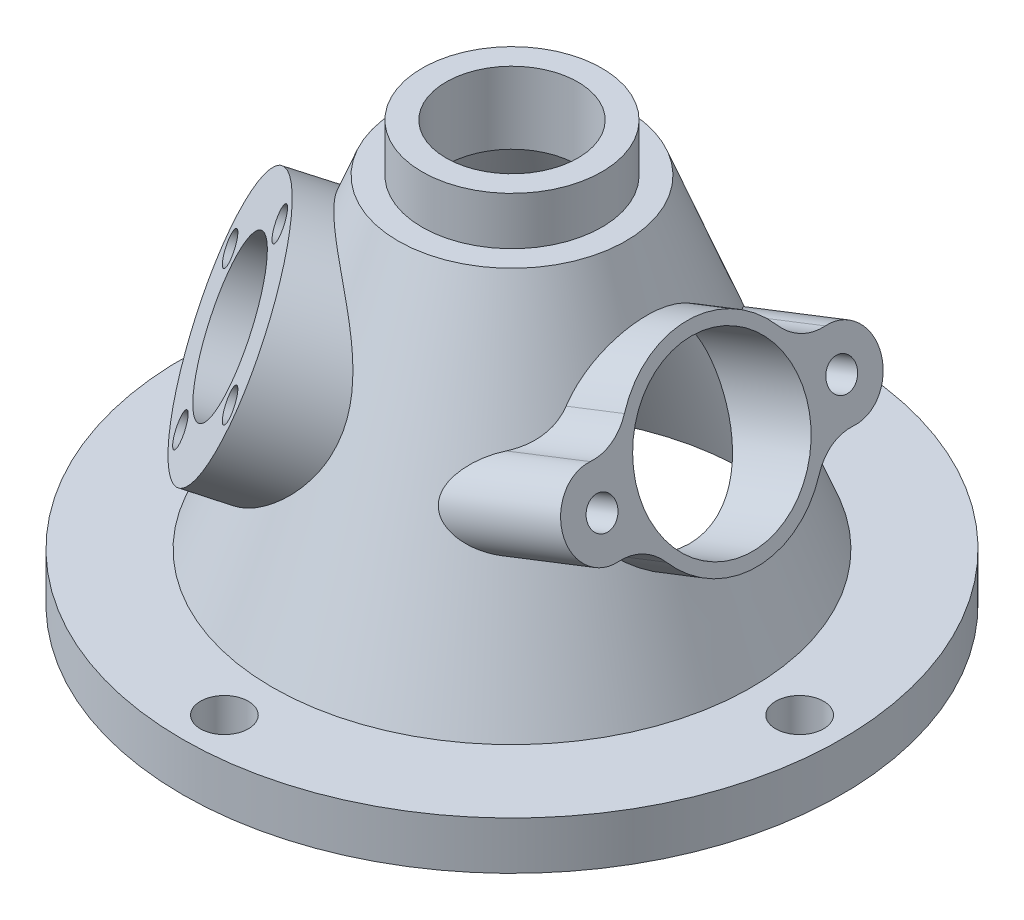
SolidWorks part; units mm, degrees
ref_plane "Front Plane" through (0, 0, 0) normal (0, 0, 1) x (1, 0, 0)
ref_plane "Top Plane" through (0, 0, 0) normal (0, 1, 0) x (1, 0, 0)
ref_plane "Right Plane" through (0, 0, 0) normal (1, 0, 0) x (0, 0, -1)
sketch "Sketch1" plane through (0, 0, 0) normal (0, 0, 1) x (1, 0, 0)
  line L0 (0, 0) -> (-11306.7437, 0) construction
  line L1 (0, 0) -> (0, -50000) construction
  line L3 (27.5, 0) -> (27.5, 4)
  line L4 (27.5, 4) -> (20, 4)
  line L5 (20, 4) -> (9.5, 31)
  line L6 (9.5, 31) -> (7.5, 31)
  line L7 (7.5, 31) -> (7.5, 35)
  line L8 (7.5, 35) -> (5.5, 35)
  line L9 (5.5, 35) -> (5.5, 29)
  line L10 (5.5, 29) -> (8.1319, 29)
  line L11 (8.1319, 29) -> (19.4096, 0)
  line L12 (19.4096, 0) -> (27.5, 0)
  dimension "D1" = 19
  dimension "D2" = 15
  dimension "D3" = 4
  dimension "D4" = 2
  dimension "D5" = 2
  dimension "D6" = 4
  dimension "D7" = 55
  dimension "D8" = 40
  dimension "D9" = 35
  dimension "D10" = 2
revolve "Revolve1" add sketch "Sketch1" angle 360 about L1
sketch "Sketch2" plane through (0, 4, 0) normal (0, 1, 0) x (1, 0, 0)
  line L0 (0, 0) -> (-50000, 0) construction
  line L1 (0, 0) -> (0, -50000) construction
  circle A0 centre (0, 24) radius 2
  circle A1 centre (24, 0) radius 2
  circle A2 centre (0, -24) radius 2
  circle A3 centre (-24, 0) radius 2
  point P7 (-25.7521, -3.72)
  point P16 (0, 0)
  dimension "D1" = 24
  dimension "D2" = 4
  dimension "D3" = 4
extrude "Cut-Extrude1" cut sketch "Sketch2" against normal blind 10
sketch "Sketch4" plane through (0, 35, 0) normal (0, 1, 0) x (1, 0, 0)
  line L0 (0, 7.5) -> (0, -7.5)
  line L1 (-5.3033, 5.3033) -> (5.3033, -5.3033)
  circle A0 centre (0, 0) radius 7.5 construction
  circle A1 centre (0, 0) radius 7.5 construction
  point P10 (0, 0)
  dimension "D1" = 45
ref_plane "Plane1" through (11.8453, 4.6183, 0) normal (0.9317, 0.3633, 0) x (0, 0, 1)
ref_plane "Plane2" through (22.0939, 8.6141, 0) normal (0.9317, 0.3633, 0) x (0, 0, 1)
sketch "Sketch5" plane through (22.0939, 8.6141, 0) normal (0.9317, 0.3633, 0) x (0, 0, 1)
  line L0 (-7.5, -32.6092) -> (7.5, -32.6092) construction
  line L1 (0, -12.6092) -> (0, 0) construction
  line L2 (-10, -12.6092) -> (10, -12.6092) construction
  arc A0 (6.3813, -7.7843) -> (-6.3813, -7.7843) centre (0, -12.6092) ccw
  circle A1 centre (0, -12.6092) radius 7
  circle A2 centre (-10, -12.6092) radius 1.25
  circle A3 centre (10, -12.6092) radius 1.25
  arc A5 (9.8081, -15.8535) -> (9.8081, -9.3649) centre (10, -12.6092) ccw
  arc A6 (-9.8081, -9.3649) -> (-9.8081, -15.8535) centre (-10, -12.6092) ccw
  arc A7 (9.8081, -15.8535) -> (6.3813, -17.4341) centre (9.5719, -19.8465) ccw
  arc A8 (9.8081, -9.3649) -> (6.3813, -7.7843) centre (9.5719, -5.3718) cw
  arc A9 (-9.8081, -9.3649) -> (-6.3813, -7.7843) centre (-9.5719, -5.3718) ccw
  arc A10 (-9.8081, -15.8535) -> (-6.3813, -17.4341) centre (-9.5719, -19.8465) cw
  arc A11 (-6.3813, -17.4341) -> (6.3813, -17.4341) centre (0, -12.6092) ccw
  point P10 (0, -12.6092)
  dimension "D1" = 20
  dimension "D2" = 16
  dimension "D3" = 14
  dimension "D5" = 2.5
  dimension "D6" = 8
  dimension "D7" = 3.25
  dimension "D4" = 20
extrude "Boss-Extrude1" add sketch "Sketch5" against normal up to next
extrude "Cut-Extrude2" cut sketch "Sketch5<3>" against normal blind 20 contours A1 | A2 | A3 region at (17.5136, 20.3619, 0) region at (17.5136, 20.3619, -10)
sketch "Sketch5<3>" plane through (22.0939, 8.6141, 0) normal (0.9317, 0.3633, 0) x (0, 0, 1) same geometry as "Sketch5"
ref_plane "Plane3" through (-8.4393, 4.7013, 8.4393) normal (-0.6579, 0.3665, 0.6579) x (0.7071, 0, 0.7071)
ref_plane "Plane4" through (-15.0183, 8.3663, 15.0183) normal (-0.6579, 0.3665, 0.6579) x (0.7071, 0, 0.7071)
sketch "Sketch7" plane through (-15.0183, 8.3663, 15.0183) normal (-0.6579, 0.3665, 0.6579) x (0.7071, 0, 0.7071)
  line L0 (0, 12.2425) -> (0, -49987.7575) construction
  line L1 (-7.5, 32.5646) -> (7.5, 32.5646) construction
  circle A0 centre (0, 12.5646) radius 10
  circle A1 centre (0, 12.5646) radius 6
  circle A2 centre (0, 12.5646) radius 8 construction
  circle A3 centre (0, 20.5646) radius 1.25
  circle A4 centre (8, 12.5646) radius 1.25
  circle A5 centre (0, 4.5646) radius 1.25
  circle A6 centre (-8, 12.5646) radius 1.25
  point P11 (0, 0)
  point P12 (-7.6386, 10.1874)
  point P13 (0, 0)
  point P20 (0, 12.5646)
  dimension "D1" = 20
  dimension "D2" = 12
  dimension "D3" = 16
  dimension "D5" = 2.5
  dimension "D4" = 20
  dimension "D6" = 4
extrude "Boss-Extrude2" add sketch "Sketch7" against normal up to next contours A4 | A6 | A5 | A0 A6 A5 A4 A3 A1 | A3 | A1 region at (-18.6332, 20.0567, 4.8911) region at (-6.1053, 20.0567, 17.419) region at (-13.8354, 12.6133, 13.8354) region at (-17.419, 20.0567, 6.1053)
extrude "Cut-Extrude3" cut sketch "Sketch7<3>" against normal blind 15 contours A1 | A4 | A3 | A5 | A6 region at (-11.7622, 20.0567, 11.7622) region at (-9.6889, 27.5, 9.6889) region at (-6.1053, 20.0567, 17.419) region at (-13.8354, 12.6133, 13.8354)
sketch "Sketch7<3>" plane through (-15.0183, 8.3663, 15.0183) normal (-0.6579, 0.3665, 0.6579) x (0.7071, 0, 0.7071) same geometry as "Sketch7"
